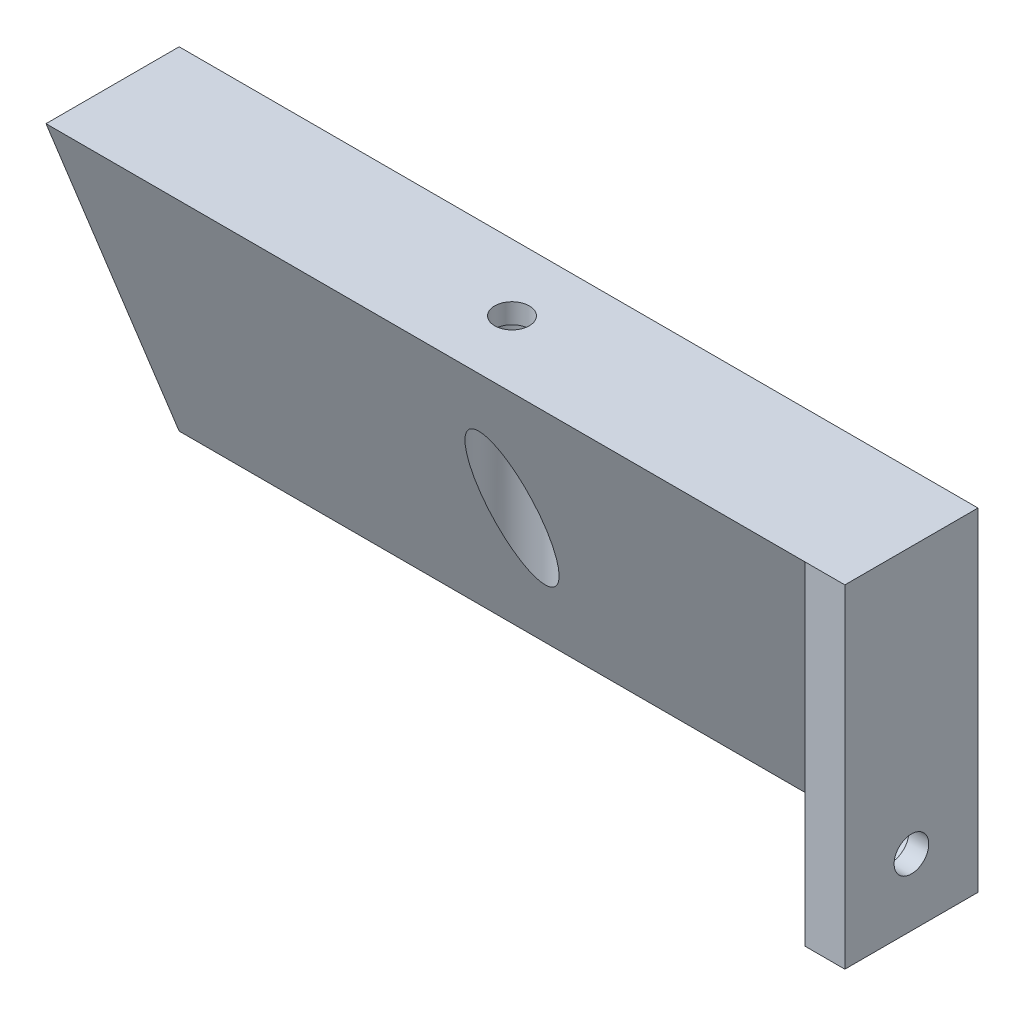
SolidWorks part; units mm, degrees
ref_plane "前视基准面" through (0, 0, 0) normal (0, 0, 1) x (1, 0, 0)
ref_plane "上视基准面" through (0, 0, 0) normal (0, 1, 0) x (1, 0, 0)
ref_plane "右视基准面" through (0, 0, 0) normal (1, 0, 0) x (0, 0, -1)
other "Configuration Table"
sketch "草图1" plane through (0, 0, 0) normal (0, 1, 0) x (1, 0, 0)
  line L1 (0, 0) -> (120, 0)
  line L2 (0, 0) -> (0, 20)
  line L3 (0, 20) -> (120, 20)
  line L4 (120, 0) -> (120, 20)
extrude "凸台-拉伸1" add sketch "草图1" along normal blind 50
sketch "草图2" plane through (0, 0, 0) normal (0, 0, 1) x (1, 0, 0)
  line L1 (0, 0) -> (6, 0)
  line L2 (0, 0) -> (0, -20)
  line L3 (0, -20) -> (6, -20)
  line L4 (6, 0) -> (6, -20)
extrude "凸台-拉伸2" add sketch "草图2" against normal blind 20
sketch "草图3" plane through (120, 0, 0) normal (1, 0, 0) x (0, 0, -1)
  line L0 (0, 50) -> (20, 0)
  line L1 (20, 0) -> (0, 0)
  line L2 (0, 0) -> (0, 50)
extrude "切除-拉伸1" cut sketch "草图3" against normal blind 114 contours L2 L0 L1
sketch "草图4" plane through (6, 0, 0) normal (1, 0, 0) x (0, 0, -1)
  line L4 (20, 0) -> (0, 0)
  line L5 (20, 0) -> (20, -20)
  line L6 (20, -20) -> (0, -20)
  line L7 (0, 0) -> (0, -20)
  circle A0 centre (10, 10) radius 2.6
extrude "切除-拉伸2" cut sketch "草图4" against normal blind 114 contours A0 | L5 L4 L7 L6
sketch "草图5" plane through (6, 0, 0) normal (1, 0, 0) x (0, 0, -1)
  circle A0 centre (10, 10) radius 5
extrude "切除-拉伸3" cut sketch "草图5" against normal blind 3
sketch "草图6" plane through (0, 50, 0) normal (0, 1, 0) x (1, 0, 0)
  line L0 (60, 20) -> (60, 0)
  line L1 (120, 20) -> (0, 20) construction
  line L2 (6, 0) -> (120, 0) construction
  circle A0 centre (60, 10) radius 2.6
extrude "切除-拉伸4" cut sketch "草图6" against normal blind 300 contours L0 A0 | L0 A0 region at (61.1035, 50, -10) region at (58.8965, 50, -10)
sketch "草图8" plane through (0, 50, 0) normal (0, 1, 0) x (1, 0, 0)
  circle A0 centre (60, 10) radius 5
extrude "切除-拉伸5" cut sketch "草图8" against normal blind 300
sketch "草图9" plane through (0, 50, 0) normal (0, 1, 0) x (1, 0, 0)
  circle A0 centre (60, 10) radius 5
  circle A1 centre (60, 10) radius 2.6
extrude "凸台-拉伸3" add sketch "草图9" against normal blind 3
mirror "镜向2" about plane through (120, 50, 0) normal (-1, 0, 0) of "切除-拉伸1", "切除-拉伸5", "凸台-拉伸1", "凸台-拉伸2", "切除-拉伸2", "切除-拉伸3", "凸台-拉伸3"
sketch "草图11" plane through (0, 50, 0) normal (0, 1, 0) x (1, 0, 0)
  line L0 (6, 0) -> (234, 0) construction
  line L1 (0, 20) -> (120, 20)
  line L2 (0, 20) -> (0, 0)
  line L3 (0, 0) -> (120, 0)
  line L4 (120, 20) -> (120, 0)
extrude "切除-拉伸6" cut sketch "草图11" against normal blind 100
